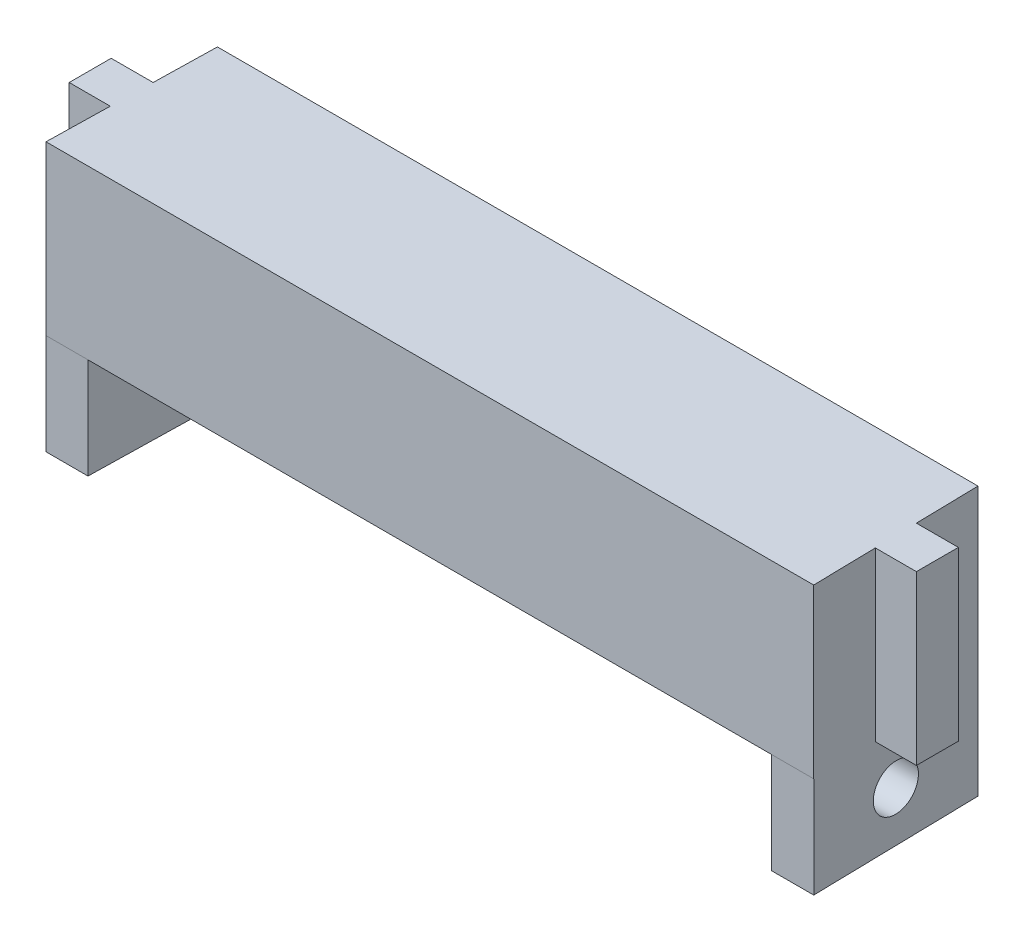
SolidWorks part; units mm, degrees
ref_plane "Front Plane" through (0, 0, 0) normal (0, 0, 1) x (1, 0, 0)
ref_plane "Top Plane" through (0, 0, 0) normal (0, 1, 0) x (1, 0, 0)
ref_plane "Right Plane" through (0, 0, 0) normal (1, 0, 0) x (0, 0, -1)
sketch "Sketch1" plane through (0, 0, 0) normal (0, 1, 0) x (1, 0, 0)
  line L0 (-45.74, 0) -> (-45.3158, 20)
  line L1 (-45.3158, 20) -> (45.3158, 20)
  line L2 (45.3158, 20) -> (45.74, 0)
  line L3 (45.74, 0) -> (-45.74, 0)
  point P4 (0, 0)
  point P7 (0, 20)
  dimension "D1" = 20
  dimension "D2" = 91.48
  dimension "D3" = 2.43
extrude "Boss-Extrude1" add sketch "Sketch1" along normal blind 20
sketch "Sketch2" plane through (0, 20, 0) normal (0, 1, 0) x (1, 0, 0)
  line L0 (45.74, 0) -> (45.3158, 20) construction
  line L1 (45.4749, 12.5) -> (50.4749, 12.5)
  line L2 (45.4749, 12.5) -> (45.4749, 7.5)
  line L3 (45.4749, 7.5) -> (50.4749, 7.5)
  line L4 (50.4749, 12.5) -> (50.4749, 7.5)
  line L5 (40.3158, 20) -> (40.3158, 0) construction
  line L6 (45.3158, 20) -> (-45.3158, 20) construction
  line L7 (-45.74, 0) -> (45.74, 0) construction
  line L8 (40.3158, 10) -> (45.5279, 10) construction
  line L9 (0, 0) -> (0, 20) construction
  line L10 (-45.4749, 7.5) -> (-50.4749, 7.5)
  line L11 (-50.4749, 12.5) -> (-50.4749, 7.5)
  line L12 (-45.4749, 12.5) -> (-50.4749, 12.5)
  line L13 (-45.4749, 12.5) -> (-45.4749, 7.5)
  point P14 (45.4749, 10)
  dimension "D1" = 5
  dimension "D2" = 5
  dimension "D3" = 5
extrude "Boss-Extrude2" add sketch "Sketch2" against normal up to surface (20 mm away) up to face at (0, 0, -10)
sketch "Sketch3" plane through (-45.7194, 0, -0.9697) normal (-0.9998, 0, -0.0212) x (-0.0212, 0, 0.9998)
  line L0 (0.9649, 0) -> (0.9649, -27.94) construction
  line L1 (-19.0346, 0) -> (0.9649, 0)
  line L2 (-19.0346, 0) -> (-19.0346, -12)
  line L3 (-19.0346, -12) -> (0.9649, -12)
  line L4 (0.9649, 0) -> (0.9649, -12)
  circle A0 centre (-9.0348, -6) radius 2.75
  point P9 (-10.3916, -5.8093)
  point P10 (-19.0346, -6)
  point P11 (-9.0348, 0)
  point P12 (-19.0346, 0)
  dimension "D2" = 5.5
  dimension "D1" = 12
ref_plane "Plane1" through (-40.7206, 0, -0.8636) normal (-0.9998, 0, -0.0212) x (-0.0212, 0, 0.9998)
sketch "Sketch4" plane through (-40.7206, 0, -0.8636) normal (-0.9998, 0, -0.0212) x (-0.0212, 0, 0.9998)
  line L4 (-19.1407, 0) -> (-19.1407, -12)
  line L5 (-19.1407, -12) -> (0.8638, -12)
  line L6 (0.8638, -12) -> (0.8638, 0)
  line L7 (0.8638, 0) -> (-19.1407, 0)
  line L11 (-19.0346, -12) -> (0.9649, -12) construction
  circle A0 centre (-9.0348, -6) radius 2.75 construction
  circle A1 centre (-9.0348, -6) radius 2.75
  point P3 (-18.7665, 0.0507)
  point P6 (0, 0)
  point P12 (0, 0)
loft "Loft1" add section "Sketch4" section "Sketch3" start constraint default connector at (-40.3147, 0, -20) connector at (-45.3158, 0, -20)
sketch "Sketch5" plane through (-40.7206, 0, -0.8636) normal (0.9998, 0, 0.0212) x (0.0212, 0, -0.9998)
  circle A0 centre (9.0348, -6) radius 2.75 construction
  circle A1 centre (9.0348, -6) radius 2.75
extrude "Cut-Extrude1" cut sketch "Sketch5" against normal through all
mirror "Mirror1" about plane through (0, 0, 0) normal (1, 0, 0) of "Cut-Extrude1", "Loft1"
